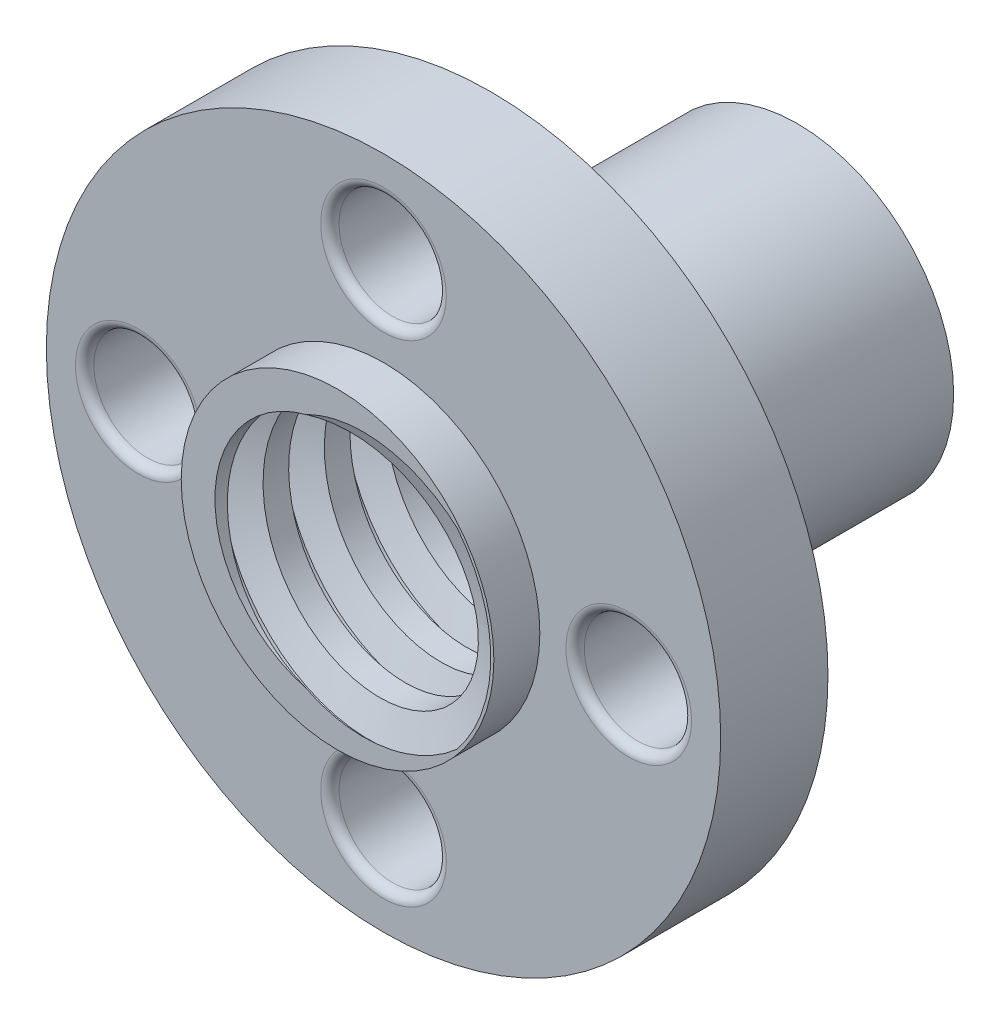
SolidWorks part; units mm, degrees
material "Brass"
ref_plane "Front Plane" through (0, 0, 0) normal (0, 0, 1) x (1, 0, 0)
ref_plane "Top Plane" through (0, 0, 0) normal (0, 1, 0) x (1, 0, 0)
ref_plane "Right Plane" through (0, 0, 0) normal (1, 0, 0) x (0, 0, -1)
sketch "Sketch1" plane through (0, 0, 0) normal (0, 0, 1) x (1, 0, 0)
  circle A0 centre (0, 0) radius 11
  circle A1 centre (0, 0) radius 5.1
  circle A2 centre (0, 0) radius 8 construction
  circle A3 centre (0, 8) radius 1.75
  circle A4 centre (8, 0) radius 1.75
  circle A5 centre (0, -8) radius 1.75
  circle A6 centre (-8, 0) radius 1.75
  point P16 (0, 0)
  dimension "D1" = 22
  dimension "D2" = 10.2
  dimension "D3" = 16
  dimension "D4" = 3.5
  dimension "D5" = 4
extrude "Boss-Extrude1" add sketch "Sketch1" against normal blind 3.5
sketch "Sketch2" plane through (0, 0, 0) normal (0, 0, 1) x (1, 0, 0)
  circle A0 centre (0, 0) radius 5.1
  circle A1 centre (0, 0) radius 4
  dimension "D1" = 8
extrude "Boss-Extrude2" add sketch "Sketch2" along normal blind 1.5 and the other way blind 13.5
sketch "Sketch3" plane through (0, 0, 1.5) normal (0, 0, 1) x (1, 0, 0)
  circle A0 centre (0, 0) radius 4
curve "Helix/Spiral1" pitch 2 height 15 radius 4 centre (0, 0, 1.5) axis (0, 0, -1) start towards (1, 0, 0)
sketch "Sketch4" plane through (0, 0, 0) normal (0, 1, 0) x (1, 0, 0)
  line L0 (3, -0.55) -> (3, -2.45)
  line L1 (3, -2.45) -> (5, -1.7146)
  line L2 (5, -1.7146) -> (5, -1.2854)
  line L3 (5, -1.2854) -> (3, -0.55)
  line L4 (3, -1.5) -> (5, -1.5)
  point P6 (4, -1.5)
  dimension "D1" = 1.9
  dimension "D2" = 2
  dimension "D3" = 69.811
sweep "Cut-Sweep1" cut profiles "Sketch4" path "Helix/Spiral1" align with end faces yes
fillet "Fillet2" radius 0.3 4 edges at (9.75, 0, 0) (1.75, -8, 0) (-6.25, 0, 0) (1.75, 8, 0)
